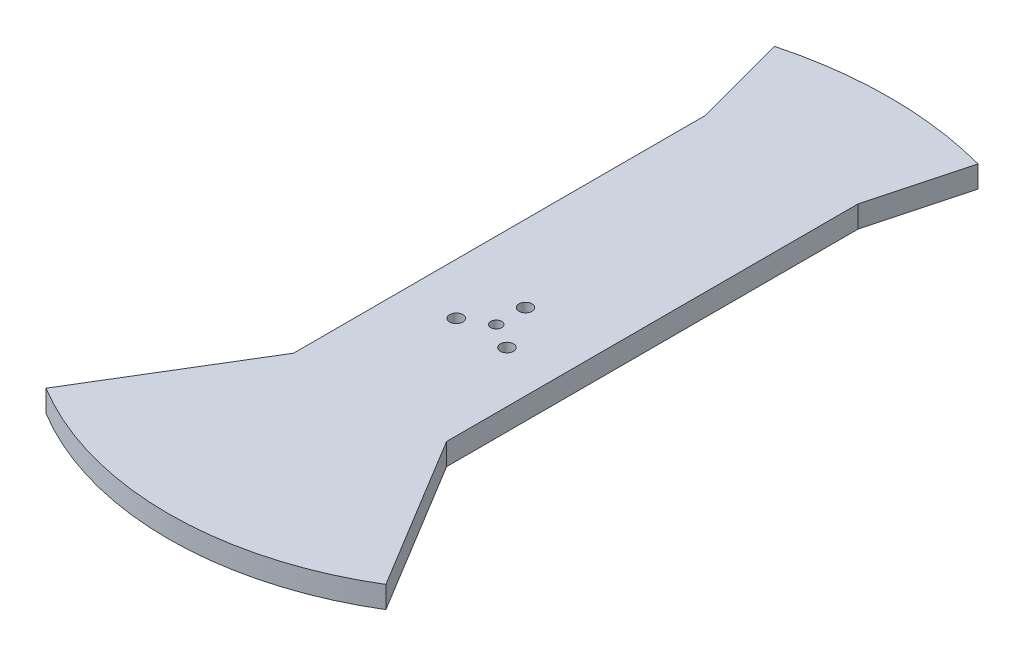
SolidWorks part; units mm, degrees
material "Plain Carbon Steel"
ref_plane "Front Plane" through (0, 0, 0) normal (0, 0, 1) x (1, 0, 0)
ref_plane "Top Plane" through (0, 0, 0) normal (0, 1, 0) x (1, 0, 0)
ref_plane "Right Plane" through (0, 0, 0) normal (1, 0, 0) x (0, 0, -1)
sketch "Sketch1" plane through (0, 0, 0) normal (0, 1, 0) x (1, 0, 0)
  line L0 (0, 114.3) -> (0, -114.3) construction
  line L1 (-5.7523, 21.4677) -> (-29.583, 110.4053) construction
  line L2 (-11.5221, -19.0051) -> (-49.3802, -81.4503) construction
  line L3 (11.5221, -19.0051) -> (49.3802, -81.4503) construction
  line L4 (5.7523, 21.4677) -> (29.583, 110.4053) construction
  line L5 (-22.225, 82.9448) -> (-22.225, -36.6591)
  line L6 (22.225, 82.9448) -> (22.225, -36.6591)
  line L7 (-29.583, 110.4053) -> (-22.225, 82.9448)
  line L8 (22.225, 82.9448) -> (29.583, 110.4053)
  line L9 (-22.225, -36.6591) -> (-49.3802, -81.4503)
  line L10 (22.225, -36.6591) -> (49.3802, -81.4503)
  circle A0 centre (0, 0) radius 22.225 construction
  circle A1 centre (0, 0) radius 114.3 construction
  circle A2 centre (0, 0) radius 95.25 construction
  arc A3 (-49.3802, -81.4503) -> (49.3802, -81.4503) centre (0, 0) ccw
  arc A4 (-29.583, 110.4053) -> (29.583, 110.4053) centre (0, 0) cw
  dimension "D1" = 44.45
  dimension "D2" = 30
  dimension "D3" = 228.6
  dimension "D4" = 190.5
  dimension "D5" = 62.454
extrude "Boss-Extrude1" add sketch "Sketch1" along normal mid plane 6.35
sketch "Sketch2" plane through (0, 3.175, 0) normal (0, 1, 0) x (1, 0, 0)
  line L0 (0, 8.5055) -> (-7.366, -4.2528) construction
  line L7 (-7.366, -4.2528) -> (7.366, -4.2528) construction
  line L8 (7.366, -4.2528) -> (0, 8.5055) construction
  line L9 (0, 8.5055) -> (0, 0) construction
  line L10 (0, 0) -> (-7.366, -4.2528) construction
  line L11 (0, 0) -> (7.366, -4.2528) construction
  circle A0 centre (0, 0) radius 1.5875
  dimension "D1" = 14.732
  dimension "D2" = 3.175
extrude "Cut-Extrude1" cut sketch "Sketch2" against normal up to next
hole_wizard "#6 Clearance Hole1" positions "Sketch4" profile "Sketch5" hole size "#6" standard "ANSI Inch" end condition up to next
sketch "Sketch4" plane through (0, 3.175, 0) normal (0, 1, 0) x (1, 0, 0)
  point P0 (0, 8.5055)
  point P3 (7.366, -4.2528)
  point P6 (-7.366, -4.2528)
sketch "Sketch5" plane through (0, 3.175, -8.5055) normal (1, 0, 0) x (0, 0, 1)
  line L0 (0, 0) -> (0, 6.35)
  line L1 (0, 6.35) -> (1.8986, 6.35)
  line L2 (1.8986, 6.35) -> (1.8986, 0)
  line L5 (1.8986, 0) -> (0, 0)
  line L11 (0, -6.35) -> (0, 107.95) construction
  dimension "Thru Hole Dia." = 3.7973
  dimension "Thru Hole Depth" = 6.35
